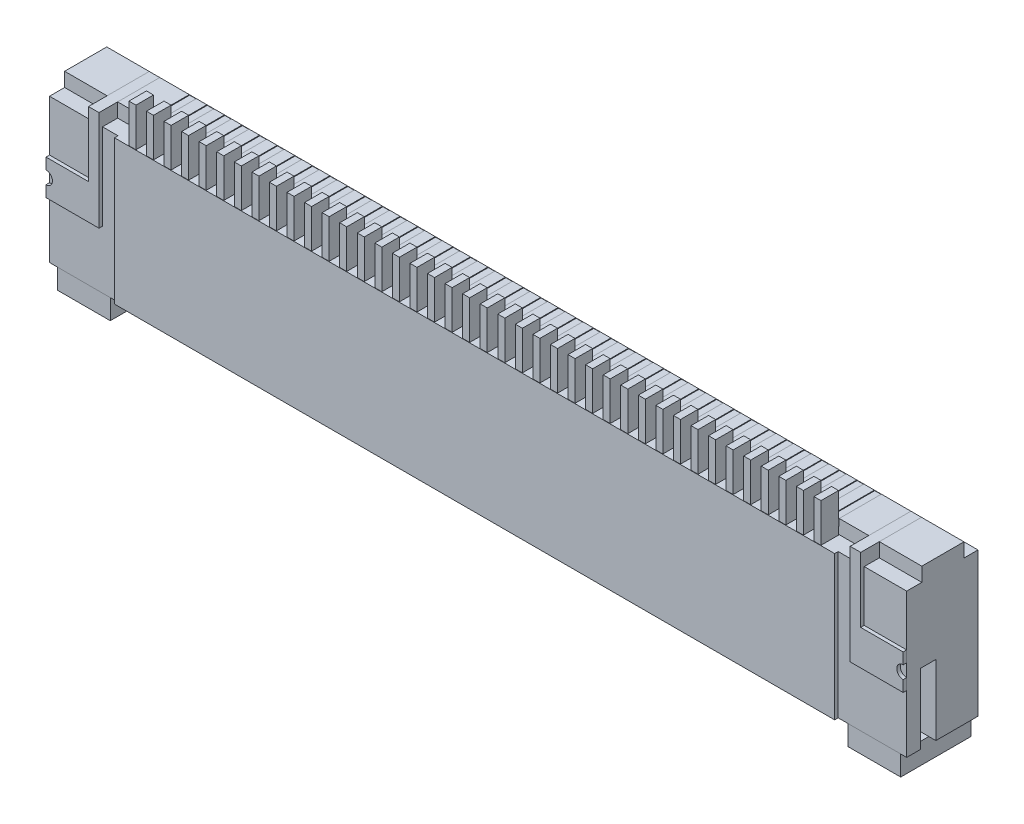
SolidWorks part; units mm, degrees
ref_plane "Plano frontal" through (0, 0, 0) normal (0, 0, 1) x (1, 0, 0)
ref_plane "Plano superior" through (0, 0, 0) normal (0, 1, 0) x (1, 0, 0)
ref_plane "Plano direito" through (0, 0, 0) normal (1, 0, 0) x (0, 0, -1)
sketch "Esboço1" plane through (0, 0, 0) normal (0, 0, 1) x (1, 0, 0)
  line L1 (-12.2, 2.25) -> (12.2, 2.25)
  line L2 (-12.2, 2.25) -> (-12.2, -2.25)
  line L3 (-12.2, -2.25) -> (12.2, -2.25)
  line L4 (12.2, 2.25) -> (12.2, -2.25)
  line L5 (-12.2, 2.25) -> (12.2, -2.25) construction
  line L6 (-12.2, -2.25) -> (12.2, 2.25) construction
  point P0 (0, 0)
  dimension "D1" = 24.4
  dimension "D2" = 4.5
extrude "Ressalto-extrusão1" add sketch "Esboço1" along normal blind 2.13
sketch "Esboço2" plane through (0, 0, 2.13) normal (0, 0, 1) x (1, 0, 0)
  line L1 (12.2, 2.25) -> (-12.2, 2.25) construction
  line L2 (0, -2.875) -> (0, 0) construction
  line L3 (-10.25, 2.25) -> (10.25, 2.25)
  line L4 (-10.25, 2.25) -> (-10.25, -2.25)
  line L5 (-10.25, -2.25) -> (10.25, -2.25)
  line L6 (10.25, 2.25) -> (10.25, -2.25)
  line L7 (-12.2, -2.25) -> (12.2, -2.25) construction
  dimension "D1" = 20.5
extrude "Corte-extrusão1" cut sketch "Esboço2" against normal blind 0.1 flip side to cut
sketch "Esboço3" plane through (0, 0, 0) normal (0, 0, -1) x (-1, 0, 0)
  line L0 (-11.5, -2.25) -> (-11.5, -0.25)
  line L1 (12.2, -2.25) -> (-12.2, -2.25) construction
  line L2 (-11.5, -0.25) -> (-10.3, -0.25)
  line L3 (-10.3, -0.25) -> (-10.3, -0.75)
  line L4 (-10.3, -0.75) -> (10.3, -0.75)
  line L5 (10.3, -0.75) -> (10.3, -0.25)
  line L6 (10.3, -0.25) -> (11.5, -0.25)
  line L7 (11.5, -0.25) -> (11.5, -2.25)
  line L8 (11.5, -2.25) -> (-11.5, -2.25)
  line L9 (-12.2, -2.25) -> (-12.2, 2.25) construction
  line L10 (12.2, 2.25) -> (12.2, -2.25) construction
  line L11 (0, 0) -> (0, -0.75) construction
  dimension "D1" = 0.7
  dimension "D2" = 0.7
  dimension "D3" = 20.6
  dimension "D4" = 2
  dimension "D5" = 1.5
extrude "Corte-extrusão2" cut sketch "Esboço3" against normal offset from surface (1.53 mm away) 0.6 up to face at (0, 0, 2.13)
sketch "Esboço4" plane through (-12.2, 0, 0) normal (-1, 0, 0) x (0, 0, 1)
  line L1 (1.2, -0.25) -> (1.63, -0.25)
  line L2 (1.2, -0.25) -> (1.2, -2.25)
  line L3 (1.2, -2.25) -> (1.63, -2.25)
  line L4 (1.63, -0.25) -> (1.63, -2.25)
  line L5 (2.03, 2.25) -> (2.03, -2.25) construction
  line L6 (0, 2.25) -> (0, -2.25) construction
  line L7 (2.03, -2.25) -> (0, -2.25) construction
  dimension "D1" = 0.4
  dimension "D2" = 1.2
  dimension "D3" = 2
extrude "Corte-extrusão3" cut sketch "Esboço4" against normal through all
sketch "Esboço5" plane through (0, 0, 1.63) normal (0, 0, -1) x (-1, 0, 0)
  line L0 (-12.2, -2.25) -> (12.2, -2.25) construction
  line L1 (11.2, -2.25) -> (10.6, -2.25)
  line L2 (11.2, -2.25) -> (11.2, -0.55)
  line L3 (11.2, -0.55) -> (10.6, -0.55)
  line L4 (10.6, -2.25) -> (10.6, -0.55)
  line L5 (11.5, -2.25) -> (11.5, -0.25) construction
  line L7 (10.3, -0.25) -> (10.3, -0.75) construction
  line L8 (-12.2, -0.25) -> (12.2, -0.25) construction
  line L9 (0, 0) -> (0, 4.9503) construction
  line L10 (-10.6, -2.25) -> (-10.6, -0.55)
  line L11 (-11.2, -0.55) -> (-10.6, -0.55)
  line L12 (-11.2, -2.25) -> (-11.2, -0.55)
  line L13 (-11.2, -2.25) -> (-10.6, -2.25)
  dimension "D1" = 0.3
  dimension "D2" = 0.3
  dimension "D3" = 0.3
extrude "Ressalto-extrusão2" add sketch "Esboço5" along normal blind 0.3
sketch "Esboço6" plane through (0, -2.25, 0) normal (0, -1, 0) x (1, 0, 0)
  line L0 (-11.5, 1.2) -> (-11.5, 0) construction
  line L1 (11.5, 1.2) -> (11.5, 0) construction
  circle A0 centre (-11.5, 0.6) radius 0.2
  circle A1 centre (11.5, 0.6) radius 0.2
  dimension "D1" = 0.4
  dimension "D2" = 0.4
extrude "Corte-extrusão4" cut sketch "Esboço6" against normal up to surface (2 mm away) up to face at (0, -0.25, 0.8717)
sketch "Esboço7" plane through (0, 0, 2.03) normal (0, 0, 1) x (1, 0, 0)
  line L0 (10.25, 2.25) -> (-10.25, 2.25) construction
  line L1 (-12, 2.25) -> (0, 2.25)
  line L2 (-12, 2.25) -> (-12, 2.85)
  line L3 (-10, 3.5) -> (10, 3.5)
  line L4 (-10.25, -2.25) -> (10.25, -2.25) construction
  line L5 (0, 0) -> (0, 3.5) construction
  line L6 (-12, 2.85) -> (-10.5, 2.85)
  line L7 (-10.5, 2.85) -> (-10, 3.5)
  line L8 (-10, 3.5) -> (10, 3.5)
  line L9 (10.5, 2.85) -> (10, 3.5)
  line L10 (12, 2.85) -> (10.5, 2.85)
  line L11 (12, 2.25) -> (12, 2.85)
  line L12 (0, 2.25) -> (12, 2.25)
  line L13 (0, 0) -> (2.2978, 0) construction
  line L14 (-12, -2.25) -> (-12, -2.85)
  line L15 (12, -2.25) -> (12, -2.85)
  line L16 (12, -2.85) -> (10.5, -2.85)
  line L17 (10.5, -2.85) -> (10, -3.5)
  line L18 (-10, -3.5) -> (10, -3.5)
  line L19 (-10.5, -2.85) -> (-10, -3.5)
  line L20 (-12, -2.85) -> (-10.5, -2.85)
  line L21 (-10, -3.5) -> (10, -3.5)
  line L22 (-12, -2.25) -> (-10.25, -2.25)
  line L23 (-10.25, -2.25) -> (-10.25, 2.25)
  line L24 (-10.25, 2.25) -> (-10.25, -2.25) construction
  line L25 (10.25, 2.25) -> (10.25, -2.25)
  line L26 (10.25, -2.25) -> (12, -2.25)
  dimension "D1" = 24
  dimension "D2" = 5.75
  dimension "D3" = 1.5
  dimension "D4" = 0.6
  dimension "D5" = 20
extrude "Ressalto-extrusão3" add sketch "Esboço7" against normal up to surface (2.03 mm away) from offset 0.03 separate body contours L26 L22 L14 L20 L19 L18 L17 L16 L15 region at (0, -0.6584, 2.03) up to face at (0, -0.5833, 0) offset against normal yes
sketch "Esboço8" plane through (0, 0, 0) normal (0, 0, -1) x (-1, 0, 0)
  line L0 (-12.2, 2.25) -> (12.2, 2.25) construction
  line L1 (-10.25, -2.25) -> (10.4244, -2.25)
  line L2 (-10.25, -2.25) -> (-10.25, 2.25)
  line L3 (-10.25, 2.25) -> (10.4244, 2.25)
  line L4 (10.4244, -2.25) -> (10.4244, 2.25)
extrude "Corte-extrusão5" cut sketch "Esboço8" against normal through all
sketch "Esboço10" plane through (0, -3.5, 0) normal (0, -1, 0) x (1, 0, 0)
  line L0 (10.5, 0) -> (10.5, 2) construction
  line L1 (-10.5, 2) -> (10.5, 2)
  line L2 (-10.5, 2) -> (-10.5, 0.6)
  line L3 (-10.5, 0.6) -> (10.5, 0.6)
  line L4 (10.5, 2) -> (10.5, 0.6)
  line L5 (10, 0) -> (-10, 0) construction
  dimension "D1" = 0.6
extrude "Corte-extrusão6" cut sketch "Esboço10" against normal up to surface (0.65 mm away) up to face at (-11.25, -2.85, 1)
sketch "Esboço11" plane through (0, -2.85, 0) normal (0, -1, 0) x (1, 0, 0)
  line L0 (12, 2) -> (-12, 2) construction
  line L1 (-10.5, 0.6) -> (10.5, 0.6)
  line L2 (-10.5, 0.6) -> (-10.5, 2)
  line L3 (-10.5, 2) -> (10.5, 2)
  line L4 (10.5, 0.6) -> (10.5, 2)
  line L5 (10.5, 0) -> (10.5, 0.6) construction
extrude "Corte-extrusão7" cut sketch "Esboço11" against normal through all
sketch "Esboço12" plane through (0, 0, 1.33) normal (0, 0, -1) x (-1, 0, 0)
  line L0 (-12, -2.25) -> (12, -2.25) construction
  line L1 (-11.35, -2.25) -> (-10.45, -2.25)
  line L2 (-11.35, -2.25) -> (-11.35, -0.4)
  line L3 (-11.35, -0.4) -> (-10.45, -0.4)
  line L4 (-10.45, -2.25) -> (-10.45, -0.4)
  line L5 (-11.5, -0.25) -> (-11.5, -2.25) construction
  line L6 (-10.3, -0.25) -> (-11.5, -0.25) construction
  line L7 (-10.3, -0.25) -> (-10.3, -0.75) construction
  line L8 (0, 0) -> (0, -1.3813) construction
  line L9 (10.45, -2.25) -> (10.45, -0.4)
  line L10 (11.35, -0.4) -> (10.45, -0.4)
  line L11 (11.35, -2.25) -> (11.35, -0.4)
  line L12 (11.35, -2.25) -> (10.45, -2.25)
  point P6 (-11.5, -1.25)
  point P11 (-10.3, -0.5)
  dimension "D1" = 0.15
  dimension "D2" = 0.15
  dimension "D3" = 0.15
extrude "Ressalto-extrusão4" add sketch "Esboço12" along normal up to surface (1.33 mm away) from offset 0.03 up to face at (0, -2.8625, 0)
sketch "Esboço13" plane through (0, 0, 0) normal (0, 0, -1) x (-1, 0, 0)
  line L0 (10.45, -2.25) -> (10.45, -0.4) construction
  line L1 (-10.45, -2.25) -> (10.45, -2.25)
  line L2 (-10.45, -2.25) -> (-10.45, -1.95)
  line L3 (-10.45, -1.95) -> (10.45, -1.95)
  line L4 (10.45, -2.25) -> (10.45, -1.95)
  dimension "D1" = 0.3
extrude "Ressalto-extrusão5" add sketch "Esboço13" against normal up to surface (0.6 mm away) up to face at (0, -2.7125, 0.6)
sketch "Esboço14" plane through (0, 0, 1.63) normal (0, 0, -1) x (-1, 0, 0)
  line L0 (0, 0) -> (0, -4.4042) construction
  line L1 (-9.75, -0.75) -> (-9.75, -2.25) construction
  line L2 (10.3, -0.75) -> (-10.3, -0.75) construction
  line L3 (9.75, -0.75) -> (9.75, -3.7346) construction
  line L4 (-9.85, -0.75) -> (-9.85, -2.25)
  line L5 (-9.65, -0.75) -> (-9.65, -2.25)
  line L6 (-9.65, -0.75) -> (-9.85, -0.75)
  line L7 (-9.85, -2.25) -> (-9.65, -2.25)
  line L9 (-9.65, -0.75) -> (-9.65, -3.7346) construction
  line L10 (-9.75, -0.75) -> (-9.75, -3.7346) construction
  line L11 (-9.85, -0.75) -> (-9.85, -3.7346) construction
  line L12 (-10.6, -2.25) -> (10.6, -2.25) construction
  dimension "D1" = 19.5
  dimension "D2" = 0.1
  dimension "D3" = 0.1
extrude "Ressalto-extrusão6" add sketch "Esboço14" along normal blind 0.5 separate body
pattern_linear "Padrão linear1" count 40 spacing 0.5 along (-1, 0, 0) of bodies 113
sketch "Esboço16" plane through (0, 0, 0) normal (0, 0, -1) x (-1, 0, 0)
  line L0 (-9.65, -2.25) -> (-9.65, -0.75) construction
  line L1 (-9.85, -0.75) -> (-9.85, -2.25) construction
  line L2 (-9.65, -2.25) -> (-9.65, -0.75)
  line L3 (-9.85, -0.75) -> (-9.85, -2.25)
  line L4 (-9.85, -2.25) -> (-9.65, -2.25)
  line L5 (-9.35, -2.25) -> (-9.15, -2.25)
  line L6 (-9.35, -0.75) -> (-9.35, -2.25)
  line L7 (-9.15, -2.25) -> (-9.15, -0.75)
  line L8 (-8.85, -2.25) -> (-8.65, -2.25)
  line L9 (-8.85, -0.75) -> (-8.85, -2.25)
  line L10 (-8.65, -2.25) -> (-8.65, -0.75)
  line L11 (-8.35, -2.25) -> (-8.15, -2.25)
  line L12 (-8.35, -0.75) -> (-8.35, -2.25)
  line L13 (-8.15, -2.25) -> (-8.15, -0.75)
  line L14 (-7.85, -2.25) -> (-7.65, -2.25)
  line L15 (-7.85, -0.75) -> (-7.85, -2.25)
  line L16 (-7.65, -2.25) -> (-7.65, -0.75)
  line L17 (-7.35, -2.25) -> (-7.15, -2.25)
  line L18 (-7.35, -0.75) -> (-7.35, -2.25)
  line L19 (-7.15, -2.25) -> (-7.15, -0.75)
  line L20 (-6.85, -2.25) -> (-6.65, -2.25)
  line L21 (-6.85, -0.75) -> (-6.85, -2.25)
  line L22 (-6.65, -2.25) -> (-6.65, -0.75)
  line L23 (-6.35, -2.25) -> (-6.15, -2.25)
  line L24 (-6.35, -0.75) -> (-6.35, -2.25)
  line L25 (-6.15, -2.25) -> (-6.15, -0.75)
  line L26 (-5.85, -2.25) -> (-5.65, -2.25)
  line L27 (-5.85, -0.75) -> (-5.85, -2.25)
  line L28 (-5.65, -2.25) -> (-5.65, -0.75)
  line L29 (-5.35, -2.25) -> (-5.15, -2.25)
  line L30 (-5.35, -0.75) -> (-5.35, -2.25)
  line L31 (-5.15, -2.25) -> (-5.15, -0.75)
  line L32 (-4.85, -2.25) -> (-4.65, -2.25)
  line L33 (-4.85, -0.75) -> (-4.85, -2.25)
  line L34 (-4.65, -2.25) -> (-4.65, -0.75)
  line L35 (-4.35, -2.25) -> (-4.15, -2.25)
  line L36 (-4.35, -0.75) -> (-4.35, -2.25)
  line L37 (-4.15, -2.25) -> (-4.15, -0.75)
  line L38 (-3.85, -2.25) -> (-3.65, -2.25)
  line L39 (-3.85, -0.75) -> (-3.85, -2.25)
  line L40 (-3.65, -2.25) -> (-3.65, -0.75)
  line L41 (-3.35, -2.25) -> (-3.15, -2.25)
  line L42 (-3.35, -0.75) -> (-3.35, -2.25)
  line L43 (-3.15, -2.25) -> (-3.15, -0.75)
  line L44 (-2.85, -2.25) -> (-2.65, -2.25)
  line L45 (-2.85, -0.75) -> (-2.85, -2.25)
  line L46 (-2.65, -2.25) -> (-2.65, -0.75)
  line L47 (-2.35, -2.25) -> (-2.15, -2.25)
  line L48 (-2.35, -0.75) -> (-2.35, -2.25)
  line L49 (-2.15, -2.25) -> (-2.15, -0.75)
  line L50 (-1.85, -2.25) -> (-1.65, -2.25)
  line L51 (-1.85, -0.75) -> (-1.85, -2.25)
  line L52 (-1.65, -2.25) -> (-1.65, -0.75)
  line L53 (-1.35, -2.25) -> (-1.15, -2.25)
  line L54 (-1.35, -0.75) -> (-1.35, -2.25)
  line L55 (-1.15, -2.25) -> (-1.15, -0.75)
  line L56 (-0.85, -2.25) -> (-0.65, -2.25)
  line L57 (-0.85, -0.75) -> (-0.85, -2.25)
  line L58 (-0.65, -2.25) -> (-0.65, -0.75)
  line L59 (-0.35, -2.25) -> (-0.15, -2.25)
  line L60 (-0.35, -0.75) -> (-0.35, -2.25)
  line L61 (-0.15, -2.25) -> (-0.15, -0.75)
  line L62 (0.15, -2.25) -> (0.35, -2.25)
  line L63 (0.15, -0.75) -> (0.15, -2.25)
  line L64 (0.35, -2.25) -> (0.35, -0.75)
  line L65 (0.65, -2.25) -> (0.85, -2.25)
  line L66 (0.65, -0.75) -> (0.65, -2.25)
  line L67 (0.85, -2.25) -> (0.85, -0.75)
  line L68 (1.15, -2.25) -> (1.35, -2.25)
  line L69 (1.15, -0.75) -> (1.15, -2.25)
  line L70 (1.35, -2.25) -> (1.35, -0.75)
  line L71 (1.65, -2.25) -> (1.85, -2.25)
  line L72 (1.65, -0.75) -> (1.65, -2.25)
  line L73 (1.85, -2.25) -> (1.85, -0.75)
  line L74 (2.15, -2.25) -> (2.35, -2.25)
  line L75 (2.15, -0.75) -> (2.15, -2.25)
  line L76 (2.35, -2.25) -> (2.35, -0.75)
  line L77 (2.65, -2.25) -> (2.85, -2.25)
  line L78 (2.65, -0.75) -> (2.65, -2.25)
  line L79 (2.85, -2.25) -> (2.85, -0.75)
  line L80 (3.15, -2.25) -> (3.35, -2.25)
  line L81 (3.15, -0.75) -> (3.15, -2.25)
  line L82 (3.35, -2.25) -> (3.35, -0.75)
  line L83 (3.65, -2.25) -> (3.85, -2.25)
  line L84 (3.65, -0.75) -> (3.65, -2.25)
  line L85 (3.85, -2.25) -> (3.85, -0.75)
  line L86 (4.15, -2.25) -> (4.35, -2.25)
  line L87 (4.15, -0.75) -> (4.15, -2.25)
  line L88 (4.35, -2.25) -> (4.35, -0.75)
  line L89 (4.65, -2.25) -> (4.85, -2.25)
  line L90 (4.65, -0.75) -> (4.65, -2.25)
  line L91 (4.85, -2.25) -> (4.85, -0.75)
  line L92 (5.15, -2.25) -> (5.35, -2.25)
  line L93 (5.15, -0.75) -> (5.15, -2.25)
  line L94 (5.35, -2.25) -> (5.35, -0.75)
  line L95 (5.65, -2.25) -> (5.85, -2.25)
  line L96 (5.65, -0.75) -> (5.65, -2.25)
  line L97 (5.85, -2.25) -> (5.85, -0.75)
  line L98 (6.15, -2.25) -> (6.35, -2.25)
  line L99 (6.15, -0.75) -> (6.15, -2.25)
  line L100 (6.35, -2.25) -> (6.35, -0.75)
  line L101 (6.65, -2.25) -> (6.85, -2.25)
  line L102 (6.65, -0.75) -> (6.65, -2.25)
  line L103 (6.85, -2.25) -> (6.85, -0.75)
  line L104 (7.15, -2.25) -> (7.35, -2.25)
  line L105 (7.15, -0.75) -> (7.15, -2.25)
  line L106 (7.35, -2.25) -> (7.35, -0.75)
  line L107 (7.65, -2.25) -> (7.85, -2.25)
  line L108 (7.65, -0.75) -> (7.65, -2.25)
  line L109 (7.85, -2.25) -> (7.85, -0.75)
  line L110 (8.15, -2.25) -> (8.35, -2.25)
  line L111 (8.15, -0.75) -> (8.15, -2.25)
  line L112 (8.35, -2.25) -> (8.35, -0.75)
  line L113 (8.65, -2.25) -> (8.85, -2.25)
  line L114 (8.65, -0.75) -> (8.65, -2.25)
  line L115 (8.85, -2.25) -> (8.85, -0.75)
  line L116 (9.15, -2.25) -> (9.35, -2.25)
  line L117 (9.15, -0.75) -> (9.15, -2.25)
  line L118 (9.35, -2.25) -> (9.35, -0.75)
  line L119 (9.65, -2.25) -> (9.85, -2.25)
  line L120 (9.65, -0.75) -> (9.65, -2.25)
  line L121 (9.85, -2.25) -> (9.85, -0.75)
  line L122 (-9.85, -0.75) -> (-9.65, -0.75)
  line L123 (9.65, -0.75) -> (9.85, -0.75)
  line L124 (9.15, -0.75) -> (9.35, -0.75)
  line L125 (8.65, -0.75) -> (8.85, -0.75)
  line L126 (8.15, -0.75) -> (8.35, -0.75)
  line L127 (7.65, -0.75) -> (7.85, -0.75)
  line L128 (6.65, -0.75) -> (6.85, -0.75)
  line L129 (7.15, -0.75) -> (7.35, -0.75)
  line L130 (6.15, -0.75) -> (6.35, -0.75)
  line L131 (5.65, -0.75) -> (5.85, -0.75)
  line L132 (5.15, -0.75) -> (5.35, -0.75)
  line L133 (4.65, -0.75) -> (4.85, -0.75)
  line L134 (4.15, -0.75) -> (4.35, -0.75)
  line L135 (3.65, -0.75) -> (3.85, -0.75)
  line L136 (3.15, -0.75) -> (3.35, -0.75)
  line L137 (2.65, -0.75) -> (2.85, -0.75)
  line L138 (2.15, -0.75) -> (2.35, -0.75)
  line L139 (1.65, -0.75) -> (1.85, -0.75)
  line L140 (1.15, -0.75) -> (1.35, -0.75)
  line L141 (0.65, -0.75) -> (0.85, -0.75)
  line L142 (0.15, -0.75) -> (0.35, -0.75)
  line L143 (-0.35, -0.75) -> (-0.15, -0.75)
  line L144 (-0.85, -0.75) -> (-0.65, -0.75)
  line L145 (-1.35, -0.75) -> (-1.15, -0.75)
  line L146 (-1.85, -0.75) -> (-1.65, -0.75)
  line L147 (-2.35, -0.75) -> (-2.15, -0.75)
  line L148 (-2.85, -0.75) -> (-2.65, -0.75)
  line L149 (-3.35, -0.75) -> (-3.15, -0.75)
  line L150 (-3.85, -0.75) -> (-3.65, -0.75)
  line L151 (-4.35, -0.75) -> (-4.15, -0.75)
  line L152 (-4.85, -0.75) -> (-4.65, -0.75)
  line L153 (-5.35, -0.75) -> (-5.15, -0.75)
  line L154 (-5.85, -0.75) -> (-5.65, -0.75)
  line L155 (-6.35, -0.75) -> (-6.15, -0.75)
  line L156 (-6.85, -0.75) -> (-6.65, -0.75)
  line L157 (-7.35, -0.75) -> (-7.15, -0.75)
  line L158 (-7.85, -0.75) -> (-7.65, -0.75)
  line L159 (-8.35, -0.75) -> (-8.15, -0.75)
  line L160 (-8.85, -0.75) -> (-8.65, -0.75)
  line L161 (-9.35, -0.75) -> (-9.15, -0.75)
  dimension "D1" = 40
extrude "Ressalto-extrusão8" add sketch "Esboço16" against normal blind 0.5 from offset 0.03 offset against normal yes
sketch "Esboço17" plane through (12.2, 0, 0) normal (1, 0, 0) x (0, 0, -1)
  line L0 (0, -2.25) -> (0, 2.25) construction
  line L1 (-0.4, 2.65) -> (0.4, 2.65)
  line L2 (-0.4, 2.65) -> (-0.4, 1.85)
  line L3 (-0.4, 1.85) -> (0.4, 1.85)
  line L4 (0.4, 2.65) -> (0.4, 1.85)
  line L5 (-0.4, 2.65) -> (0.4, 1.85) construction
  line L6 (-0.4, 1.85) -> (0.4, 2.65) construction
  line L7 (-2.46, 2.65) -> (-1.6, 2.65)
  line L8 (-2.46, 2.65) -> (-2.46, 1.85)
  line L9 (-2.46, 1.85) -> (-1.6, 1.85)
  line L10 (-1.6, 2.65) -> (-1.6, 1.85)
  line L11 (-2.46, 2.65) -> (-1.6, 1.85) construction
  line L12 (-2.46, 1.85) -> (-1.6, 2.65) construction
  line L13 (-2.03, 2.25) -> (0, 2.25) construction
  point P0 (0, 2.25)
  point P6 (-2.03, 2.25)
  dimension "D1" = 1.2
  dimension "D2" = 0.4
  dimension "D3" = 0.4
  dimension "D4" = 0.4
extrude "Corte-extrusão8" cut sketch "Esboço17" against normal through all
sketch "Esboço19" plane through (0, 0, 2.13) normal (0, 0, 1) x (1, 0, 0)
  line L0 (-12.2, 1.85) -> (-12.2, -2.25) construction
  line L1 (-12.2, 0.4) -> (-10.9908, 0.4)
  line L2 (-12.2, 0.4) -> (-12.2, -0.6)
  line L3 (-12.2, -0.6) -> (-10.9908, -0.6)
  line L4 (-10.9908, 0.4) -> (-10.9908, -0.6)
  line L5 (-12.2, 2.25) -> (12.2, 2.25) construction
  line L6 (-10.9908, -0.6) -> (-10.6908, -0.6)
  line L7 (-10.9908, -0.6) -> (-10.9908, 2.25)
  line L8 (-10.9908, 2.25) -> (-10.6908, 2.25)
  line L9 (-10.6908, -0.6) -> (-10.6908, 2.25)
  dimension "D1" = 1
  dimension "D2" = 2.85
  dimension "D3" = 0.3
sketch "Esboço20" plane through (0, 0, 1.6) normal (0, 0, 1) x (1, 0, 0)
  line L0 (-10.6908, -0.6) -> (-10.6908, 2.25) construction
  line L1 (-10.9908, 2.25) -> (-10.6908, 2.25)
  line L2 (-10.9908, 2.25) -> (-10.9908, 1.95)
  line L3 (-10.9908, 1.95) -> (-10.6908, 1.95)
  line L4 (-10.6908, 2.25) -> (-10.6908, 1.95)
  dimension "D1" = 0.3
extrude "Corte-extrusão9" cut sketch "Esboço20" against normal blind 10
mirror "Espelhar1" about plane through (0, 0, 0) normal (1, 0, 0) of "Corte-extrusão9"
extrude "Ressalto-extrusão9" add sketch "Esboço19" against normal up to surface (0.1 mm away) separate body contours L4 L1 L2 L3 | L6 L9 L8 L7 L4 region at (-11.5954, -0.1, 2.13) region at (-10.8408, 0.825, 2.13) up to face at (-11.225, -0.2, 2.03)
sketch "Esboço21" plane through (0, 0, 2.03) normal (0, 0, -1) x (-1, 0, 0)
  line L0 (10.9908, 2.25) -> (10.9908, 0.4) construction
  line L1 (10.6908, 2.25) -> (10.9908, 2.25)
  line L2 (10.6908, 2.25) -> (10.6908, 1.85)
  line L3 (10.6908, 1.85) -> (10.9908, 1.85)
  line L4 (10.9908, 2.25) -> (10.9908, 1.85)
  line L5 (12.2, 1.85) -> (10.25, 1.85) construction
extrude "Ressalto-extrusão10" add sketch "Esboço21" along normal up to surface (0.43 mm away) up to face at (0, 2.0833, 1.6)
sketch "Esboço22" plane through (0, 0, 1.6) normal (0, 0, -1) x (-1, 0, 0)
  line L0 (10.6908, 1.95) -> (10.6908, 2.25) construction
  line L1 (10.9908, 1.95) -> (10.6908, 1.95) construction
  line L2 (10.9908, 2.25) -> (10.9908, 1.95) construction
  line L3 (10.6908, 1.95) -> (10.6908, 2.25)
  line L4 (10.9908, 1.95) -> (10.6908, 1.95)
  line L5 (10.9908, 2.25) -> (10.9908, 1.95)
  line L6 (10.9908, 2.25) -> (10.6908, 2.25) construction
  line L7 (10.9908, 2.25) -> (10.6908, 2.25)
extrude "Ressalto-extrusão11" add sketch "Esboço22" along normal up to surface (1.2 mm away) up to face at (0, 2.0833, 0.4)
sketch "Esboço23" plane through (0, 0, 2.13) normal (0, 0, 1) x (1, 0, 0)
  line L0 (-12.2, 0.4) -> (-12.2, -0.6) construction
  circle A0 centre (-12.2, -0.1) radius 0.1829
extrude "Corte-extrusão10" cut sketch "Esboço23" against normal blind 10
mirror "Espelhar2" about plane through (0, 0, 0) normal (1, 0, 0) of bodies 161
sketch "Esboço24" plane through (0, 0, 2.13) normal (0, 0, 1) x (1, 0, 0)
  line L0 (-10.25, 1.85) -> (10.25, 1.85) construction
  line L1 (-9.85, 1.85) -> (-9.65, 1.85)
  line L2 (-9.85, 1.85) -> (-9.85, 2.95)
  line L3 (-9.85, 2.95) -> (-9.65, 2.95)
  line L4 (-9.65, 1.85) -> (-9.65, 2.95)
  line L5 (0, 0) -> (0, 4.6196) construction
  line L6 (-9.75, 2.95) -> (-9.75, 1.85) construction
  line L7 (-10.6908, 2.25) -> (10.6908, 2.25) construction
  dimension "D1" = 0.2
  dimension "D2" = 19.5
  dimension "D3" = 0.7
extrude "Ressalto-extrusão12" add sketch "Esboço24" against normal blind 0.5 from offset 0.01 offset against normal yes
pattern_linear "Padrão linear2" count 40 spacing 0.5 along (1, 0, 0) of "Ressalto-extrusão12"
sketch "Esboço25" plane through (0, 2.25, 0) normal (0, 1, 0) x (1, 0, 0)
  line L0 (-12.2, -0.4) -> (12.2, -0.4) construction
  line L1 (-9.85, -1.62) -> (-9.65, -1.62)
  line L2 (-9.85, -1.62) -> (-9.85, -0.4)
  line L3 (-9.85, -0.4) -> (-9.65, -0.4)
  line L4 (-9.65, -1.62) -> (-9.65, -0.4)
  line L5 (-9.65, -1.62) -> (-9.65, -2.12) construction
extrude "Corte-extrusão11" cut sketch "Esboço25" against normal blind 0.2
pattern_linear "Padrão linear3" count 40 spacing 0.5 along (1, 0, 0) of "Corte-extrusão11"
sketch "Esboço27" plane through (0, 0, 1.62) normal (0, 0, -1) x (-1, 0, 0)
  line L0 (9.66, 2.24) -> (9.84, 2.24)
  line L1 (9.65, 2.05) -> (9.85, 2.05)
  line L2 (9.65, 2.05) -> (9.65, 2.25)
  line L3 (9.65, 2.25) -> (9.85, 2.25)
  line L4 (9.85, 2.05) -> (9.85, 2.25)
  line L5 (9.84, 2.06) -> (9.84, 2.24)
  line L6 (9.66, 2.06) -> (9.84, 2.06)
  line L7 (9.66, 2.06) -> (9.66, 2.24)
  dimension "D1" = 0.01
extrude "Ressalto-extrusão14" add sketch "Esboço27" along normal up to surface (1.22 mm away) contours L7 L6 L5 L0 region at (-9.75, 2.15, 1.62) up to face at (0, 2.1453, 0.4)
pattern_linear "Padrão linear4" count 40 spacing 0.5 along (1, 0, 0) of "Ressalto-extrusão14"
